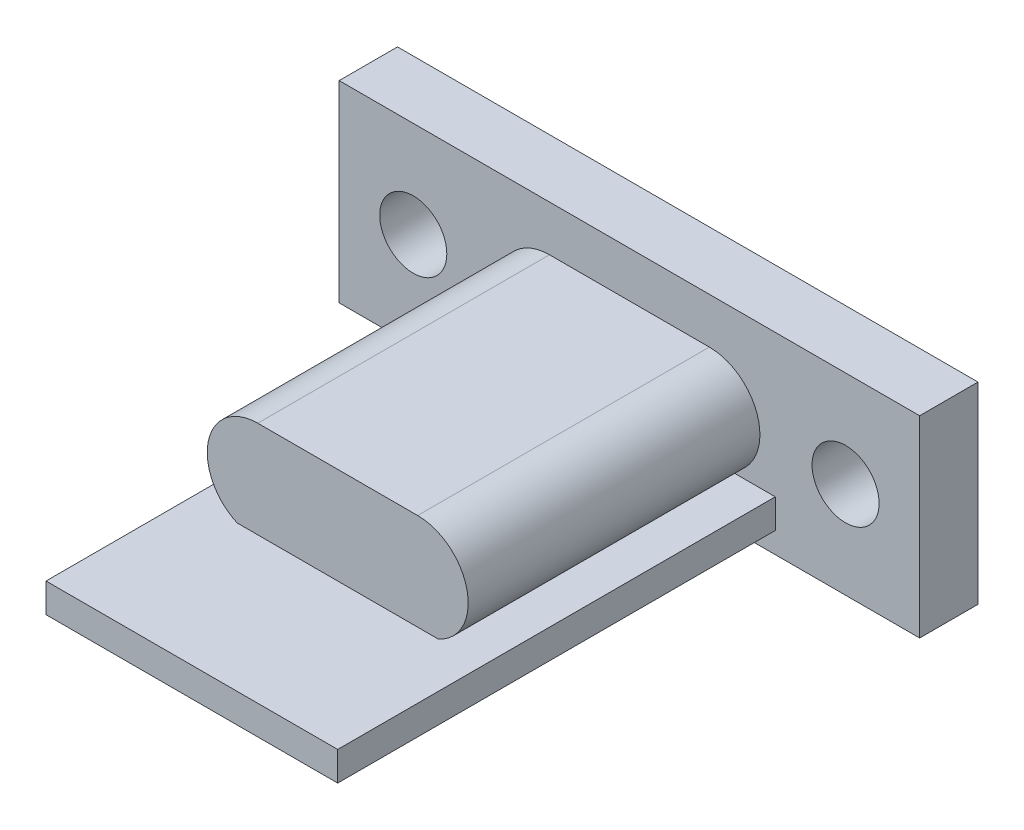
SolidWorks part; units mm, degrees
ref_plane "Front Plane" through (0, 0, 0) normal (0, 0, 1) x (1, 0, 0)
ref_plane "Top Plane" through (0, 0, 0) normal (0, 1, 0) x (1, 0, 0)
ref_plane "Right Plane" through (0, 0, 0) normal (1, 0, 0) x (0, 0, -1)
sketch "Sketch1" plane through (0, 0, 0) normal (0, 0, 1) x (1, 0, 0)
  line L0 (0, 3.3) -> (19.9, 3.3) construction
  line L1 (0, 0) -> (19.9, 0)
  line L2 (0, 0) -> (0, 6.6)
  line L3 (0, 6.6) -> (19.9, 6.6)
  line L4 (19.9, 0) -> (19.9, 6.6)
  line L5 (7.21, 3.3) -> (12.69, 3.3) construction
  line L6 (7.21, 4.88) -> (12.69, 4.88)
  line L7 (7.21, 1.72) -> (12.69, 1.72)
  circle A0 centre (2.54, 3.3) radius 1.15
  circle A1 centre (17.36, 3.3) radius 1.15
  arc A2 (7.21, 4.88) -> (7.21, 1.72) centre (7.21, 3.3) ccw
  arc A3 (12.69, 1.72) -> (12.69, 4.88) centre (12.69, 3.3) ccw
  point P11 (9.95, 3.3)
  point P18 (5.63, 3.3)
  point P19 (14.27, 3.3)
  dimension "D3" = 2.3
  dimension "D4" = 2.3
  dimension "D5" = 2.54
  dimension "D8" = 3.16
  dimension "D1" = 19.9
  dimension "D2" = 6.6
  dimension "D6" = 2.54
  dimension "D7" = 8.64
extrude "Boss-Extrude1" add sketch "Sketch1" along normal blind 2
sketch "Sketch6" plane through (0, 0, 2) normal (0, 0, 1) x (1, 0, 0)
  line L0 (7.21, 3.3) -> (12.69, 3.3) construction
  line L1 (7.21, 5.0331) -> (12.69, 5.0331)
  line L3 (7.21, 3.3) -> (12.69, 3.3) construction
  line L4 (7.21, 4.57) -> (12.69, 4.57)
  line L5 (7.21, 2.03) -> (12.69, 2.03)
  line L6 (0, 0) -> (19.9, 0) construction
  line L7 (4.95, 1.7181) -> (6.502, 1.7181)
  line L8 (4.95, 1.7181) -> (4.95, 0.7181)
  line L9 (4.95, 0.7181) -> (14.95, 0.7181)
  line L10 (14.95, 1.7181) -> (14.95, 0.7181)
  line L11 (13.398, 1.7181) -> (14.95, 1.7181)
  arc A0 (7.21, 5.0331) -> (6.502, 1.7181) centre (7.21, 3.3) ccw
  arc A1 (13.398, 1.7181) -> (12.69, 5.0331) centre (12.69, 3.3) ccw
  arc A2 (7.21, 4.57) -> (7.21, 2.03) centre (7.21, 3.3) ccw
  arc A3 (12.69, 2.03) -> (12.69, 4.57) centre (12.69, 3.3) ccw
  point P4 (9.95, 3.3)
  point P11 (9.95, 3.3)
  point P22 (9.95, 0)
  point P23 (9.95, 0.7181)
  dimension "D1" = 2.54
  dimension "D2" = 10
  dimension "D3" = 1
extrude "Boss-Extrude11" add sketch "Sketch6" along normal blind 10
sketch "Sketch7" plane through (0, 0, 12) normal (0, 0, 1) x (1, 0, 0)
  line L0 (7.21, 3.3) -> (12.69, 3.3) construction
  line L1 (7.21, 5.0331) -> (12.69, 5.0331)
  line L2 (7.21, 1.5669) -> (12.69, 1.5669)
  line L3 (12.69, 5.0331) -> (7.21, 5.0331) construction
  arc A0 (7.21, 5.0331) -> (7.21, 1.5669) centre (7.21, 3.3) ccw
  arc A1 (12.69, 1.5669) -> (12.69, 5.0331) centre (12.69, 3.3) ccw
  point P4 (9.95, 3.3)
extrude "Boss-Extrude12" add sketch "Sketch7" against normal blind 1
sketch "Sketch8" plane through (0, 0, 12) normal (0, 0, 1) x (1, 0, 0)
  line L1 (4.95, 1.7181) -> (14.95, 1.7181)
  line L2 (4.95, 1.7181) -> (4.95, 0.7181)
  line L3 (4.95, 0.7181) -> (14.95, 0.7181)
  line L4 (14.95, 1.7181) -> (14.95, 0.7181)
extrude "Boss-Extrude13" add sketch "Sketch8" along normal blind 5
